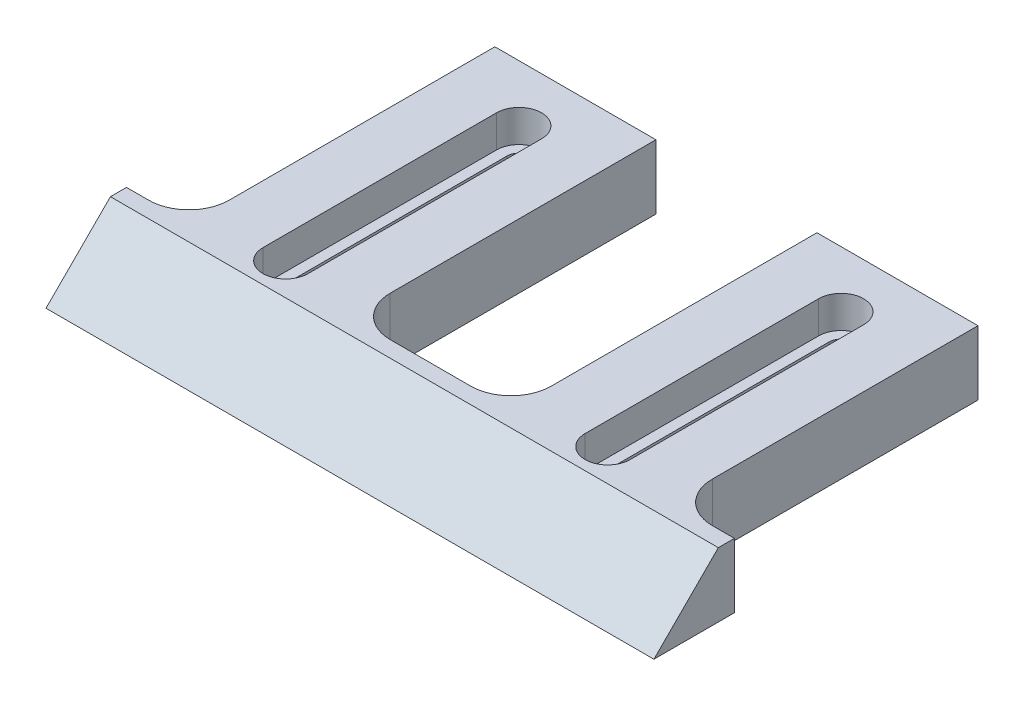
SolidWorks part; units mm, degrees
material "POM Acetal Copolymer"
ref_plane "Front Plane" through (0, 0, 0) normal (0, 0, 1) x (1, 0, 0)
ref_plane "Top Plane" through (0, 0, 0) normal (0, 1, 0) x (1, 0, 0)
ref_plane "Right Plane" through (0, 0, 0) normal (1, 0, 0) x (0, 0, -1)
sketch "Sketch1" plane through (0, 0, 0) normal (0, 1, 0) x (1, 0, 0)
  line L0 (0, 0) -> (0, 50)
  line L1 (0, 50) -> (75.5, 50)
  line L2 (75.5, 50) -> (75.5, 0)
  line L3 (75.5, 0) -> (37.75, 0)
  line L4 (37.75, 0) -> (0, 0)
  dimension "D1" = 50
  dimension "D2" = 90
  dimension "D3" = 75.5
extrude "Boss-Extrude1" add sketch "Sketch1" along normal blind 8
sketch "Sketch4" plane through (0, 8, 0) normal (0, 1, 0) x (1, 0, 0)
  line L0 (17.75, 43) -> (17.75, 14) construction
  line L1 (19.25, 43) -> (19.25, 14)
  line L2 (16.25, 43) -> (16.25, 14)
  line L3 (57.75, 43) -> (57.75, 14) construction
  line L4 (59.25, 43) -> (59.25, 14)
  line L5 (56.25, 43) -> (56.25, 14)
  line L8 (0, 50) -> (0, 0) construction
  line L9 (75.5, 50) -> (0, 50) construction
  arc A0 (19.25, 43) -> (16.25, 43) centre (17.75, 43) ccw
  arc A1 (16.25, 14) -> (19.25, 14) centre (17.75, 14) ccw
  arc A2 (59.25, 43) -> (56.25, 43) centre (57.75, 43) ccw
  arc A3 (56.25, 14) -> (59.25, 14) centre (57.75, 14) ccw
  point P2 (17.75, 28.5)
  point P7 (57.75, 28.5)
  dimension "D1" = 3
  dimension "D2" = 3
  dimension "D3" = 40
  dimension "D4" = 17.75
  dimension "D5" = 14
  dimension "D6" = 7
extrude "Cut-Extrude2" cut sketch "Sketch4" against normal up to next
sketch "Sketch5" plane through (0, 8, 0) normal (0, 1, 0) x (1, 0, 0)
  line L0 (75.5, 50) -> (0, 50) construction
  line L1 (27.75, 50) -> (47.75, 50)
  line L2 (27.75, 50) -> (27.75, 12)
  line L3 (27.75, 12) -> (47.75, 12)
  line L4 (47.75, 50) -> (47.75, 12)
  line L7 (67.75, 50) -> (75.5, 50)
  line L8 (0, 50) -> (7.75, 50)
  line L9 (0, 50) -> (0, 12)
  line L10 (0, 12) -> (7.75, 12)
  line L11 (7.75, 50) -> (7.75, 12)
  line L12 (67.75, 50) -> (67.75, 12)
  line L13 (67.75, 12) -> (75.5, 12)
  line L14 (75.5, 50) -> (75.5, 12)
  arc A0 (19.25, 43) -> (16.25, 43) centre (17.75, 43) ccw construction
  arc A1 (59.25, 43) -> (56.25, 43) centre (57.75, 43) ccw construction
  dimension "D4" = 10
  dimension "D5" = 10
  dimension "D1" = 20
  dimension "D2" = 20
  dimension "D3" = 12
extrude "Cut-Extrude3" cut sketch "Sketch5" against normal blind 10
fillet "Fillet1" radius 5 4 edges at (67.75, 4, -12) (47.75, 4, -12) (27.75, 4, -12) (7.75, 4, -12)
chamfer "Chamfer1" distance 10 angle 45 1 edges at (37.75, 8, 0)
sketch "Sketch7" plane through (0, 8, 0) normal (0, 1, 0) x (1, 0, 0)
  line L0 (17.75, 43) -> (17.75, 14) construction
  line L1 (20.55, 43) -> (20.55, 14)
  line L2 (14.95, 43) -> (14.95, 14)
  line L3 (57.75, 43) -> (57.75, 14) construction
  line L4 (60.55, 43) -> (60.55, 14)
  line L5 (54.95, 43) -> (54.95, 14)
  arc A0 (20.55, 43) -> (14.95, 43) centre (17.75, 43) ccw
  arc A1 (14.95, 14) -> (20.55, 14) centre (17.75, 14) ccw
  arc A2 (60.55, 43) -> (54.95, 43) centre (57.75, 43) ccw
  arc A3 (54.95, 14) -> (60.55, 14) centre (57.75, 14) ccw
  point P4 (17.75, 28.5)
  point P9 (57.75, 28.5)
  dimension "D1" = 5.6
  dimension "D2" = 5.6
extrude "Cut-Extrude4" cut sketch "Sketch7" against normal blind 4
